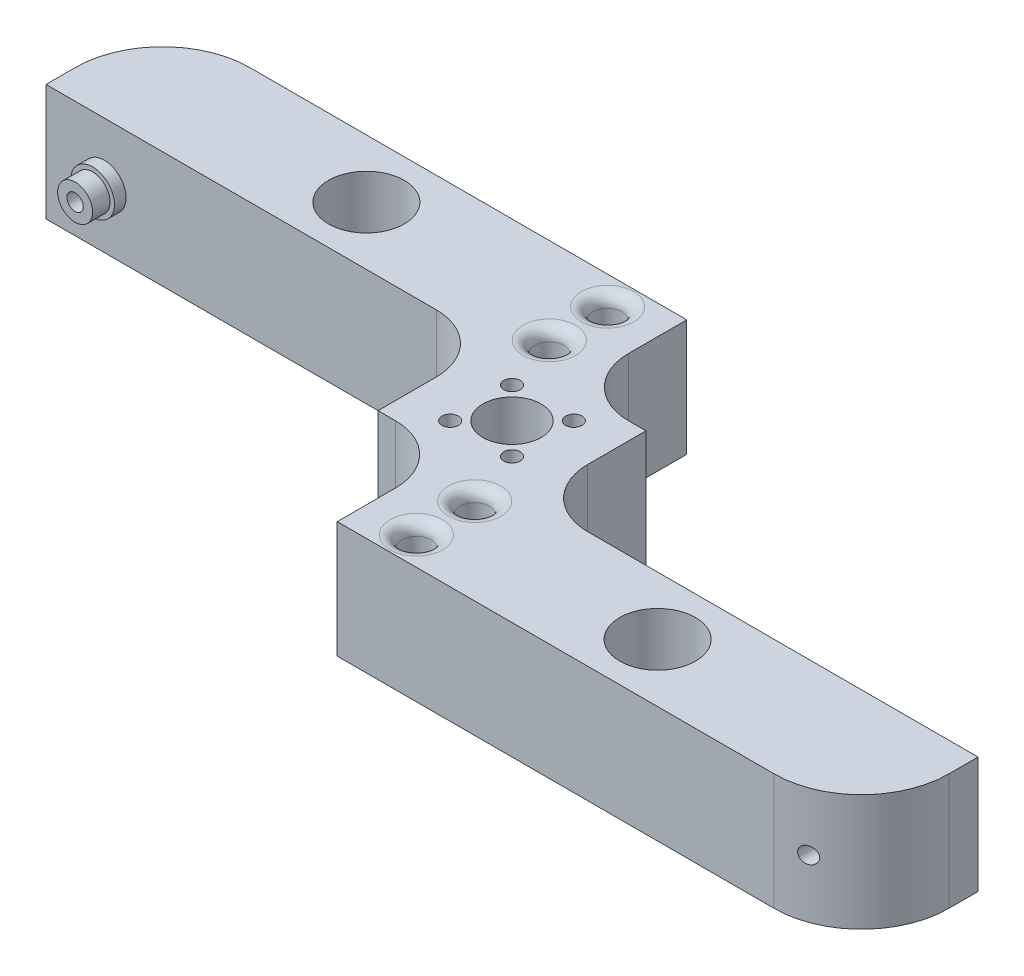
SolidWorks part; units mm, degrees
ref_plane "Front Plane" through (0, 0, 0) normal (0, 0, 1) x (1, 0, 0)
ref_plane "Top Plane" through (0, 0, 0) normal (0, 1, 0) x (1, 0, 0)
ref_plane "Right Plane" through (0, 0, 0) normal (1, 0, 0) x (0, 0, -1)
sketch "Sketch1" plane through (0, 0, 0) normal (0, 1, 0) x (1, 0, 0)
  line L0 (-90, 10) -> (-90, 30)
  line L1 (-90, -10) -> (0, -10)
  line L2 (-90, -10) -> (-90, 10)
  line L3 (0, 10) -> (90, 10)
  line L4 (90, -10) -> (90, 10)
  line L5 (-90, -10) -> (90, 10) construction
  line L6 (-90, 10) -> (90, -10) construction
  line L7 (-90, 30) -> (0, 30)
  line L8 (0, 30) -> (0, 10)
  line L9 (0, -10) -> (0, -30)
  line L10 (0, -30) -> (90, -30)
  line L11 (90, -30) -> (90, -10)
  line L12 (0, -10) -> (0, 0) construction
  line L13 (0, 0) -> (0, 10) construction
  point P0 (0, 0)
  dimension "D1" = 20
  dimension "D2" = 180
  dimension "D3" = 20
  dimension "D4" = 20
extrude "Boss-Extrude1" add sketch "Sketch1" along normal blind 20
sketch "Sketch2" plane through (0, 20, 0) normal (0, 1, 0) x (1, 0, 0)
  line L0 (-5.3033, 5.3033) -> (0, 0) construction
  line L1 (0, 0) -> (5.3033, -5.3033) construction
  line L2 (-5.3033, -5.3033) -> (0, 0) construction
  line L3 (0, 0) -> (5.3033, 5.3033) construction
  line L4 (-5.3033, 5.3033) -> (5.3033, 5.3033) construction
  circle A0 centre (0, 0) radius 5
  circle A1 centre (-5.3033, 5.3033) radius 1.4
  circle A2 centre (5.3033, 5.3033) radius 1.4
  circle A3 centre (5.3033, -5.3033) radius 1.4
  circle A4 centre (-5.3033, -5.3033) radius 1.4
  dimension "D1" = 10
  dimension "D2" = 2.8
  dimension "D3" = 15
extrude "Cut-Extrude1" cut sketch "Sketch2" against normal through all
sketch "Sketch3" plane through (0, 20, 0) normal (0, 1, 0) x (1, 0, 0)
  line L0 (0, 30) -> (-90, 30) construction
  line L1 (-90, -10) -> (-13, -10)
  line L2 (-90, -10) -> (-90, 10)
  line L3 (-90, 10) -> (-13, 10)
  line L4 (-13, -10) -> (-13, 10)
  dimension "D1" = 20
  dimension "D2" = 77
extrude "Cut-Extrude2" cut sketch "Sketch3" against normal through all
mirror "Mirror1" about plane through (0, 0, 0) normal (1, 0, 0) of "Cut-Extrude2"
sketch "Sketch4" plane through (0, 0, -10) normal (0, 0, 1) x (1, 0, 0)
  line L0 (-80, 10) -> (-90, 10) construction
  line L1 (-90, 0) -> (-90, 20) construction
  circle A0 centre (-80, 10) radius 3.75
  dimension "D1" = 7.5
  dimension "D2" = 10
extrude "Boss-Extrude2" add sketch "Sketch4" along normal blind 2
sketch "Sketch5" plane through (0, 0, -8) normal (0, 0, 1) x (1, 0, 0)
  circle A0 centre (-80, 10) radius 3
  dimension "D1" = 6
extrude "Boss-Extrude3" add sketch "Sketch5" along normal blind 3
sketch "Sketch6" plane through (0, 0, -5) normal (0, 0, 1) x (1, 0, 0)
  circle A0 centre (-80, 10) radius 1.4
  dimension "D1" = 2.8
extrude "Cut-Extrude3" cut sketch "Sketch6" against normal through all
sketch "Sketch7" plane through (0, 0, 10) normal (0, 0, -1) x (-1, 0, 0)
  line L0 (-90, 10) -> (-80, 10) construction
  line L1 (-90, 0) -> (-90, 20) construction
  circle A0 centre (-80, 10) radius 3.75
  dimension "D1" = 7.5
  dimension "D2" = 10
extrude "Boss-Extrude4" add sketch "Sketch7" along normal blind 2
sketch "Sketch8" plane through (0, 0, 8) normal (0, 0, -1) x (-1, 0, 0)
  circle A0 centre (-80, 10) radius 3
  dimension "D1" = 6
extrude "Boss-Extrude5" add sketch "Sketch8" along normal blind 3
sketch "Sketch9" plane through (0, 0, 5) normal (0, 0, -1) x (-1, 0, 0)
  circle A0 centre (-80, 10) radius 1.4
  dimension "D1" = 2.8
extrude "Cut-Extrude4" cut sketch "Sketch9" against normal through all
sketch "Sketch11" plane through (0, 20, 0) normal (0, 1, 0) x (1, 0, 0)
  line L0 (-13, -10) -> (-26, 10)
  line L1 (-13, 10) -> (-90, 10) construction
  line L2 (-26, 10) -> (-13, 10)
  line L3 (-13, 10) -> (-13, -10)
  line L4 (-13, -10) -> (0, -30)
  line L5 (0, -30) -> (0, -10)
  line L6 (0, -10) -> (0, -30) construction
  line L7 (-13, -10) -> (0, -10) construction
  line L8 (0, -10) -> (-13, -10)
  line M18 (-90, 10) -> (-13, 10)
  line M19 (-13, 10) -> (-13, -10)
  line M20 (-13, -10) -> (0, -10)
  line M21 (0, -10) -> (0, -30)
extrude "Boss-Extrude6" [suppressed] add sketch "Sketch11" against normal up to surface (20 mm away) contours L0 M19 M18 | L4 M20 M21
fillet "Fillet1" radius 10 4 edges at (0, 10, -10) (13, 10, 10) (0, 10, 10) (-13, 10, -10)
sketch "Sketch12" plane through (0, 20, 0) normal (0, 1, 0) x (1, 0, 0)
  line L0 (-8.75, 25.1554) -> (-8.75, 15.1554) construction
  line L1 (8.75, -15.1554) -> (8.75, -25.1554) construction
  line L2 (-8.75, 15.1554) -> (8.75, -15.1554) construction
  circle A0 centre (8.75, -15.1554) radius 2.5
  circle A1 centre (8.75, -25.1554) radius 2.5
  circle A2 centre (-8.75, 25.1554) radius 2.5
  circle A3 centre (-8.75, 15.1554) radius 2.5
  point P8 (0, 0)
  dimension "D1" = 5
  dimension "D2" = 10
  dimension "D3" = 35
  dimension "D4" = 150
extrude "Cut-Extrude5" cut sketch "Sketch12" against normal through all both
fillet "Fillet2" radius 2 4 edges at (8.75, 20, 27.6554) (8.75, 20, 17.6554) (-8.75, 20, -12.6554) (-8.75, 20, -22.6554)
fillet "Fillet3" radius 2 4 edges at (8.75, 0, 27.6554) (8.75, 0, 17.6554) (-8.75, 0, -12.6554) (-8.75, 0, -22.6554)
sketch "Sketch13" plane through (0, 20, 0) normal (0, 1, 0) x (1, 0, 0)
  line L0 (-45, 20) -> (45, -20) construction
  circle A0 centre (-45, 20) radius 6.5
  circle A1 centre (45, -20) radius 6.5
  point P4 (0, 0)
  dimension "D1" = 13
  dimension "D2" = 45
  dimension "D3" = 20
extrude "Cut-Extrude6" cut sketch "Sketch13" against normal through all both and the other way through all
fillet "Fillet4" radius 15 2 edges at (90, 10, 30) (-90, 10, -30)
